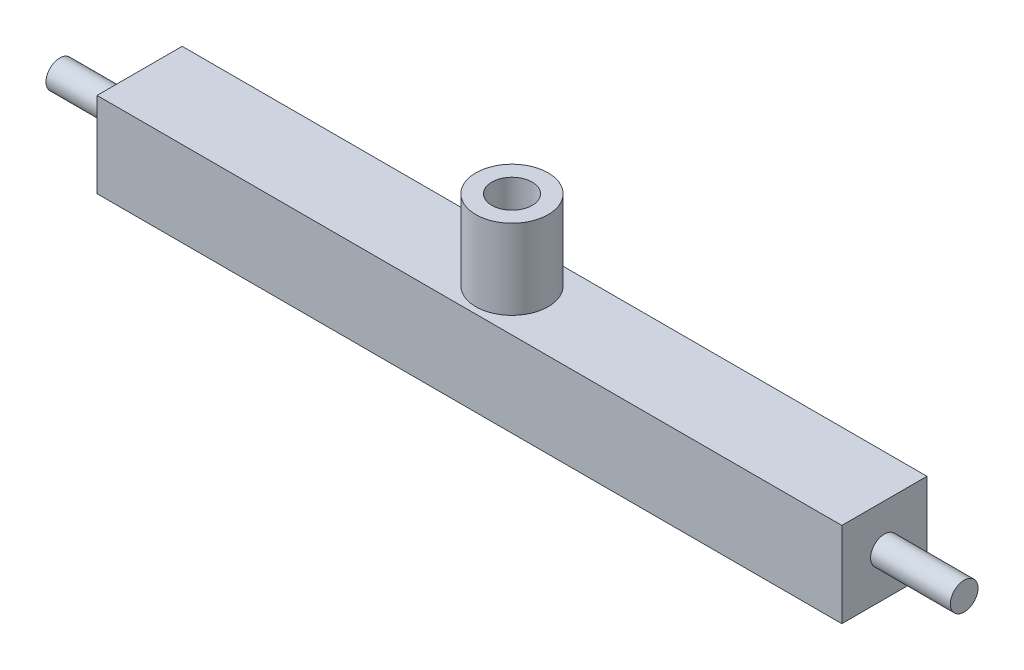
SolidWorks part; units mm, degrees
ref_plane "Front Plane" through (0, 0, 0) normal (0, 0, 1) x (1, 0, 0)
ref_plane "Top Plane" through (0, 0, 0) normal (0, 1, 0) x (1, 0, 0)
ref_plane "Right Plane" through (0, 0, 0) normal (1, 0, 0) x (0, 0, -1)
sketch "Sketch1" plane through (0, 0, 0) normal (1, 0, 0) x (0, 0, -1)
  line L1 (0, 0) -> (10.16, 0)
  line L2 (0, 0) -> (0, 10.16)
  line L3 (0, 10.16) -> (10.16, 10.16)
  line L4 (10.16, 0) -> (10.16, 10.16)
  dimension "D1" = 10.16
  dimension "D2" = 10.16
extrude "Boss-Extrude1" add sketch "Sketch1" along normal blind 88.9
sketch "Sketch2" plane through (88.9, 0, 0) normal (1, 0, 0) x (0, 0, -1)
  circle A0 centre (5.08, 5.08) radius 1.651
  dimension "D1" = 3.302
extrude "Boss-Extrude2" add sketch "Sketch2" along normal blind 9.525
ref_plane "Plane1" through (44.45, 0, 0) normal (1, 0, 0) x (0, 0, -1)
mirror "Mirror1" about plane through (44.45, 0, 0) normal (1, 0, 0) of "Boss-Extrude2"
sketch "Sketch3" plane through (0, 10.16, 0) normal (0, 1, 0) x (1, 0, 0)
  circle A0 centre (44.45, 5.08) radius 4.318
  dimension "D1" = 8.636
extrude "Boss-Extrude3" add sketch "Sketch3" along normal blind 9.525
sketch "Sketch4" plane through (0, 19.685, 0) normal (0, 1, 0) x (1, 0, 0)
  circle A0 centre (44.45, 5.08) radius 2.413
  dimension "D1" = 4.826
extrude "Cut-Extrude1" cut sketch "Sketch4" against normal blind 6.35
